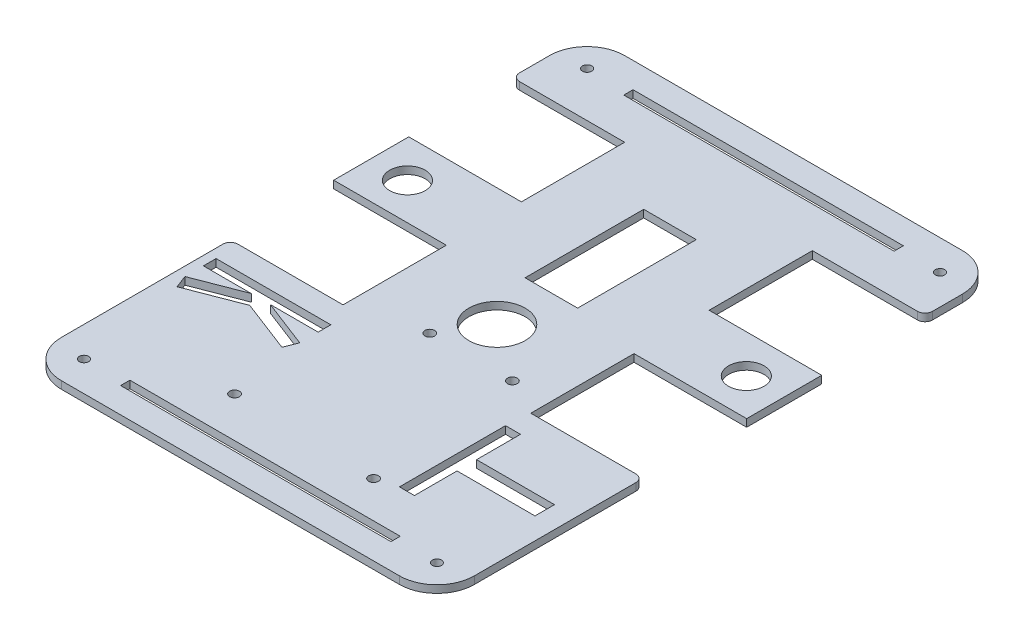
SolidWorks part; units mm, degrees
material "ABS"
ref_plane "Front Plane" through (0, 0, 0) normal (0, 0, 1) x (1, 0, 0)
ref_plane "Top Plane" through (0, 0, 0) normal (0, 1, 0) x (1, 0, 0)
ref_plane "Right Plane" through (0, 0, 0) normal (1, 0, 0) x (0, 0, -1)
sketch "Sketch2" plane through (0, 0, 0) normal (0, 1, 0) x (1, 0, 0)
  line L0 (-148.7583, 0) -> (98.0966, 0) construction
  line L1 (-69.85, -95.25) -> (69.85, -95.25)
  line L2 (-69.85, -95.25) -> (-69.85, 95.25)
  line L3 (-69.85, 95.25) -> (69.85, 95.25)
  line L4 (69.85, -95.25) -> (69.85, 95.25)
  line L5 (-69.85, -95.25) -> (69.85, 95.25) construction
  line L6 (-69.85, 95.25) -> (69.85, -95.25) construction
  line L7 (0, 121.1686) -> (0, -125.6862) construction
  point P0 (0, 0)
  dimension "D1" = 190.5
  dimension "D2" = 139.7
extrude "Base Plate" add sketch "Sketch2" along normal blind 2.54
sketch "Sketch4" plane through (0, 2.54, 0) normal (0, 1, 0) x (1, 0, 0)
  line L0 (0, -95.25) -> (0, 95.25) construction
  line L1 (-69.85, -95.25) -> (69.85, -95.25) construction
  line L2 (69.85, 95.25) -> (-69.85, 95.25) construction
  line L3 (-34.66, -69.85) -> (-34.66, -40.894) construction
  line L4 (-34.66, -40.894) -> (-58.79, -40.894) construction
  line L5 (-58.79, -40.894) -> (-58.79, -69.85) construction
  line L6 (-58.79, -69.85) -> (-34.66, -69.85) construction
  line L7 (69.85, -95.25) -> (69.85, 95.25) construction
  line L8 (-69.85, 95.25) -> (-69.85, -95.25) construction
  circle A0 centre (-58.79, -69.85) radius 1.8415
  circle A1 centre (-34.66, -69.85) radius 1.8415
  circle A2 centre (-34.66, -40.894) radius 1.8415
  circle A3 centre (-58.79, -40.894) radius 1.8415
  circle A4 centre (34.66, -69.85) radius 1.8415
  circle A5 centre (58.79, -69.85) radius 1.8415
  circle A6 centre (58.79, -40.894) radius 1.8415
  circle A7 centre (34.66, -40.894) radius 1.8415
  point P0 (-58.79, -69.85)
  point P1 (-58.79, -40.894)
  point P2 (-34.66, -40.894)
  point P3 (-34.66, -69.85)
  dimension "D4" = 3.683
  dimension "D1" = 28.956
  dimension "D2" = 24.13
  dimension "D3" = 11.06
  dimension "D5" = 25.4
sketch "Sketch5" plane through (0, 2.54, 0) normal (0, 1, 0) x (1, 0, 0)
  line L0 (-69.85, -25.4) -> (-31.75, -25.4)
  line L1 (-69.85, 95.25) -> (-69.85, -95.25) construction
  line L2 (-31.75, -25.4) -> (-31.75, 69.85)
  line L3 (-31.75, 69.85) -> (-69.85, 69.85)
  line L4 (-69.85, 69.85) -> (-69.85, -25.4)
  line L5 (-69.85, -95.25) -> (69.85, -95.25) construction
  line L6 (69.85, 95.25) -> (-69.85, 95.25) construction
  line L7 (0, -95.25) -> (0, 95.25) construction
  line L9 (31.75, 69.85) -> (69.85, 69.85)
  line L10 (31.75, -25.4) -> (31.75, 69.85)
  line L11 (69.85, -25.4) -> (31.75, -25.4)
  line L12 (69.85, 69.85) -> (69.85, -25.4)
  dimension "D1" = 25.4
  dimension "D2" = 95.25
  dimension "D3" = 38.1
extrude "Steering Wheels Holes" cut sketch "Sketch5" against normal blind 6.35
fillet "Fillet1" radius 12.7 4 edges at (69.85, 1.27, -95.25) (-69.85, 1.27, -95.25) (69.85, 1.27, 95.25) (-69.85, 1.27, 95.25)
fillet "Fillet2" radius 2.54 4 edges at (69.85, 1.27, -69.85) (69.85, 1.27, 25.4) (-69.85, 1.27, 25.4) (-69.85, 1.27, -69.85)
sketch "Sketch6" plane through (0, 2.54, 0) normal (0, 1, 0) x (1, 0, 0)
  line L0 (-69.85, -95.25) -> (-69.85, 95.25) construction
  line L1 (-69.85, -95.25) -> (69.85, -95.25) construction
  line L2 (0, -88.935) -> (0, 95.5267) construction
  line L3 (-69.85, -27.94) -> (69.85, -27.94) construction
  point P0 (-59.69, -85.09)
  point P12 (-59.69, 29.21)
  point P13 (59.69, -85.09)
  point P14 (59.69, 29.21)
  dimension "D1" = 10.16
  dimension "D2" = 10.16
sketch "Sketch15" plane through (0, 2.54, 0) normal (0, 1, 0) x (1, 0, 0)
  line L0 (-69.85, -95.25) -> (-69.85, 95.25) construction
  line L1 (-69.85, 95.25) -> (69.85, 95.25) construction
  line L2 (0, 95.25) -> (0, 49.0943) construction
  line L3 (0, 121.1686) -> (0, -125.6862) construction
  point P0 (-59.69, 85.09)
  point P5 (59.69, 85.09)
  dimension "D1" = 10.16
  dimension "D2" = 10.16
sketch "Sketch18" plane through (0, 2.54, 0) normal (0, 1, 0) x (1, 0, 0)
  line L0 (0, 95.25) -> (0, -95.25) construction
  line L1 (57.15, 95.25) -> (-57.15, 95.25) construction
  line L2 (-57.15, -95.25) -> (57.15, -95.25) construction
  line L3 (-24.003, -69.85) -> (78.9561, -69.85) construction
  circle A0 centre (-8.763, -19.05) radius 1.651
  circle A1 centre (19.177, -19.05) radius 1.651
  circle A2 centre (-24.003, -69.85) radius 1.651
  circle A3 centre (24.3097, -71.12) radius 1.651
  point P6 (-8.763, -19.05)
  point P7 (19.177, -19.05)
  point P8 (-24.003, -69.85)
  point P9 (24.257, -64.77)
  dimension "D7" = 3.302
  dimension "D1" = 52.07
  dimension "D2" = 1.27
  dimension "D3" = 5.08
  dimension "D4" = 27.94
  dimension "D5" = 15.24
  dimension "D6" = 50.8
  dimension "D8" = 114.3
extrude "Holes for Arduino UNO" cut sketch "Sketch18" against normal through all
sketch "Sketch20" plane through (0, 2.54, 0) normal (0, 1, 0) x (1, 0, 0)
  line L0 (0, 95.25) -> (0, -95.25) construction
  line L1 (57.15, 95.25) -> (-57.15, 95.25) construction
  line L2 (-57.15, -95.25) -> (57.15, -95.25) construction
  circle A0 centre (0, -5.08) radius 9.525
  dimension "D1" = 19.05
  dimension "D2" = 90.17
extrude "Cutout for motor wires" cut sketch "Sketch20" against normal through all
sketch "Sketch21" plane through (0, 2.54, 0) normal (0, 1, 0) x (1, 0, 0)
  line L0 (-31.75, 22.225) -> (31.75, 22.225) construction
  line L1 (-31.75, -25.4) -> (-31.75, 69.85) construction
  line L2 (31.75, 69.85) -> (31.75, -25.4) construction
  line L3 (0, 95.25) -> (0, -21.3651) construction
  line L4 (57.15, 95.25) -> (-57.15, 95.25) construction
  point P6 (-21.59, 22.225)
  point P12 (21.59, 22.225)
  dimension "D1" = 10.16
sketch "Sketch24" plane through (0, 2.54, 0) normal (0, 1, 0) x (1, 0, 0)
  line L0 (0, -95.25) -> (0, 95.25) construction
  line L1 (-57.15, -95.25) -> (57.15, -95.25) construction
  line L2 (57.15, 95.25) -> (-57.15, 95.25) construction
  line L3 (-69.85, 82.55) -> (-69.85, 72.39) construction
  circle A0 centre (-59.69, 85.09) radius 1.57
  circle A1 centre (-59.69, 85.09) radius 2.84
  dimension "D1" = 3.14
  dimension "D2" = 10.16
  dimension "D3" = 10.16
  dimension "D4" = 1.27
extrude "Cut-Extrude1" cut sketch "Sketch24" against normal blind 2.54 contours A0 region at (-59.69, 2.54, -85.09)
mirror "Mirror1" about plane through (0, 0, 0) normal (1, 0, 0) of "Cut-Extrude1"
sketch "Sketch25" plane through (0, 2.54, 0) normal (0, 1, 0) x (1, 0, 0)
  line L0 (0, -95.25) -> (0, 95.25) construction
  line L1 (-57.15, -95.25) -> (57.15, -95.25) construction
  line L2 (57.15, 95.25) -> (-57.15, 95.25) construction
  line L3 (-69.85, -27.94) -> (-69.85, -82.55) construction
  circle A0 centre (-59.69, -85.09) radius 1.57
  circle A2 centre (59.69, -85.09) radius 1.57
  dimension "D1" = 3.14
  dimension "D4" = 3.14
  dimension "D2" = 10.16
  dimension "D3" = 10.16
extrude "Cut-Extrude3" cut sketch "Sketch25" against normal blind 2.54
sketch "Sketch27" plane through (0, 2.54, 0) normal (0, 1, 0) x (1, 0, 0)
  line L12 (0, -95.25) -> (0, 166.7066) construction
  line L13 (-57.15, -95.25) -> (57.15, -95.25) construction
  line L14 (-59.69, -87.93) -> (59.69, -87.93) construction
  line L15 (59.69, -82.25) -> (-59.69, -82.25) construction
  line L16 (-45.72, -86.66) -> (45.72, -86.66)
  line L17 (-46.99, -87.93) -> (46.99, -87.93)
  line L18 (-46.99, -87.93) -> (-46.99, -82.25)
  line L19 (-46.99, -82.25) -> (46.99, -82.25)
  line L20 (46.99, -87.93) -> (46.99, -82.25)
  line L21 (45.72, -86.66) -> (45.72, -83.52)
  line L22 (-45.72, -83.52) -> (45.72, -83.52)
  line L23 (-45.72, -86.66) -> (-45.72, -83.52)
  line L24 (-59.69, 82.25) -> (59.69, 82.25) construction
  line L25 (59.69, 87.93) -> (-59.69, 87.93) construction
  line L26 (-45.72, 86.66) -> (45.72, 86.66)
  line L27 (-46.99, 82.25) -> (46.99, 82.25)
  line L28 (-46.99, 82.25) -> (-46.99, 87.93)
  line L29 (-46.99, 87.93) -> (46.99, 87.93)
  line L30 (46.99, 82.25) -> (46.99, 87.93)
  line L31 (45.72, 83.52) -> (45.72, 86.66)
  line L32 (-45.72, 83.52) -> (45.72, 83.52)
  line L33 (-45.72, 83.52) -> (-45.72, 86.66)
  circle A8 centre (-59.69, -85.09) radius 2.84
  circle A9 centre (-59.69, -85.09) radius 1.57 construction
  circle A10 centre (59.69, -85.09) radius 2.84
  circle A11 centre (-59.69, 85.09) radius 2.84
  circle A12 centre (-59.69, 85.09) radius 1.57 construction
  circle A13 centre (59.69, 85.09) radius 2.84
  dimension "D1" = 1.27
  dimension "D5" = 1.27
  dimension "D6" = 12.7
  dimension "D7" = 12.7
  dimension "D2" = 12.7
  dimension "D3" = 12.7
  dimension "D4" = 1.27
  dimension "D8" = 1.27
extrude "Cut-Extrude4" cut sketch "Sketch27" against normal blind 2.54 contours L23 L16 L21 L22 | L26 L31 L32 L33 region at (0, 2.54, 85.09)
sketch "Sketch28" plane through (0, 2.54, 0) normal (0, 1, 0) x (1, 0, 0)
  line L0 (-31.75, 9.525) -> (-69.85, 9.525)
  line L1 (-31.75, -25.4) -> (-31.75, 69.85) construction
  line L2 (-69.85, 9.525) -> (-69.85, 34.925)
  line L3 (-69.85, 34.925) -> (-31.75, 34.925)
  line L4 (-31.75, 9.525) -> (-31.75, 34.925)
  line L5 (-69.85, -27.94) -> (-69.85, -82.55) construction
  point P6 (-31.75, 22.225)
  point P10 (-31.75, 22.225)
  dimension "D1" = 25.4
extrude "Boss-Extrude1" add sketch "Sketch28" against normal through all
mirror "Mirror2" about plane through (0, 0, 0) normal (1, 0, 0) of "Boss-Extrude1"
sketch "Sketch29" plane through (0, 0, 0) normal (0, -1, 0) x (1, 0, 0)
  line L0 (-69.85, -34.925) -> (-69.85, -9.525) construction
  circle A0 centre (-57.3106, -21.9452) radius 6
  dimension "D1" = 12
  dimension "D2" = 12.5394
extrude "Cut-Extrude5" cut sketch "Sketch29" against normal through all contours A0
mirror "Mirror3" about plane through (0, 0, 0) normal (1, 0, 0) of "Cut-Extrude5"
sketch "Sketch30" plane through (0, 0, 0) normal (0, -1, 0) x (1, 0, 0)
  line L0 (-57.3106, -21.9452) -> (57.3106, -21.9452) construction
  line L1 (8.89, -60.0452) -> (-8.89, -60.0452)
  line L2 (8.89, -60.0452) -> (8.89, -6.7052)
  line L3 (8.89, -6.7052) -> (-8.89, -6.7052)
  line L4 (-8.89, -60.0452) -> (-8.89, -6.7052)
  line L5 (8.89, -60.0452) -> (-8.89, -6.7052) construction
  line L6 (8.89, -6.7052) -> (-8.89, -60.0452) construction
  line L7 (0, 88.935) -> (0, -95.5267) construction
  line L8 (-8.89, -53.4412) -> (8.89, -53.4412)
  line L9 (-8.89, -13.3092) -> (8.89, -13.3092)
  point P0 (0, -33.3752)
  point P9 (0, -6.7052)
  dimension "D1" = 17.78
  dimension "D2" = 53.34
  dimension "D3" = 15.24
  dimension "D4" = 6.604
  dimension "D5" = 6.604
  dimension "D6" = 40.132
extrude "Cut-Extrude6" cut sketch "Sketch30" against normal through all contours L9 L4 L8 L2 region at (0, 0, -33.3752)
sketch "Sketch31" plane through (0, 0, 0) normal (0, -1, 0) x (1, 0, 0)
  line L0 (-47.3732, 37.6063) -> (-47.3732, 54.7726) construction
  line L1 (-66.7828, 33.3147) -> (-27.9636, 33.3147)
  line L2 (-66.7828, 33.3147) -> (-66.7828, 37.6063)
  line L3 (-66.7828, 37.6063) -> (-50.5919, 37.6063)
  line L4 (-27.9636, 33.3147) -> (-27.9636, 37.6063)
  line L5 (-50.5919, 37.6063) -> (-66.7828, 43.8486)
  line L6 (-66.7828, 43.8486) -> (-65.1152, 48.1741)
  line L7 (-65.1152, 48.1741) -> (-47.3732, 41.3338)
  line L10 (-44.1545, 37.6063) -> (-27.9636, 43.8486)
  line L11 (-27.9636, 43.8486) -> (-29.6313, 48.1741)
  line L12 (-29.6313, 48.1741) -> (-47.3732, 41.3338)
  line L14 (-44.1545, 37.6063) -> (-27.9636, 37.6063)
  line L15 (31.1215, 33.3147) -> (36.1902, 33.3147)
  line L16 (36.1902, 33.3147) -> (36.1902, 48.1741)
  line L17 (36.1902, 48.1741) -> (62.5471, 48.1741)
  line L18 (62.5471, 48.1741) -> (62.5471, 54.7726)
  line L19 (62.5471, 54.7726) -> (36.1902, 54.7726)
  line L20 (36.1902, 54.7726) -> (36.1902, 69.2008)
  line L21 (36.1902, 69.2008) -> (31.1215, 69.2008)
  line L22 (31.1215, 69.2008) -> (31.1215, 33.3147)
extrude "Cut-Extrude7" cut sketch "Sketch31" against normal blind 2.54
